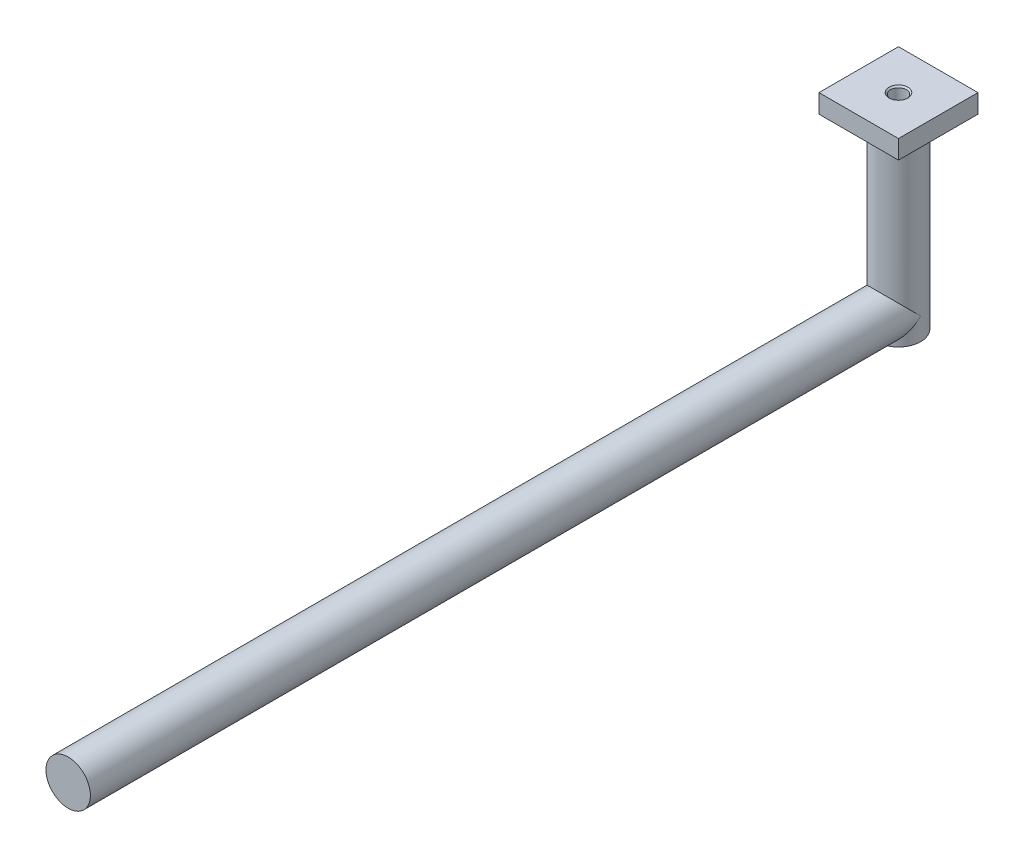
SolidWorks part; units mm, degrees
ref_plane "Front Plane" through (0, 0, 0) normal (0, 0, 1) x (1, 0, 0)
ref_plane "Top Plane" through (0, 0, 0) normal (0, 1, 0) x (1, 0, 0)
ref_plane "Right Plane" through (0, 0, 0) normal (1, 0, 0) x (0, 0, -1)
sketch "Sketch2" plane through (0, 0, 0) normal (0, 0, 1) x (1, 0, 0)
  circle A0 centre (0, 0) radius 9.5
  dimension "D1" = 19
extrude "Boss-Extrude1" add sketch "Sketch2" along normal blind 355
sketch "Sketch3" plane through (0, 0, 0) normal (0, 1, 0) x (1, 0, 0)
  circle A0 centre (0, 0) radius 9.5
  dimension "D1" = 19
extrude "Boss-Extrude2" add sketch "Sketch3" along normal blind 70
extrude "Boss-Extrude3" add sketch "Sketch3<2>" against normal blind 9.5
sketch "Sketch3<2>" plane through (0, 0, 0) normal (0, 1, 0) x (1, 0, 0) same geometry as "Sketch3"
sketch "Sketch5" plane through (0, 70, 0) normal (0, 1, 0) x (1, 0, 0)
  line L0 (-17, 17) -> (17, 17)
  line L5 (-17, 17) -> (-17, -17)
  line L6 (17, 17) -> (17, -17)
  line L7 (-17, -17) -> (17, -17)
  line L8 (-17, 17) -> (17, -17) construction
  line L9 (17, 17) -> (-17, -17) construction
  point P1 (0, 0)
  dimension "D1" = 34
  dimension "D2" = 34
extrude "Boss-Extrude4" add sketch "Sketch5" along normal blind 8
hole_wizard "M8x1.25 Tapped Hole1" positions "3DSketch1" profile "Sketch6" tap size "M8x1.25" standard "ANSI Metric" end condition through all
sketch3d "3DSketch1"
  line L0 (-17, 78, -17) -> (17, 78, 17) construction
  line L2 (-17, 78, 17) -> (17, 78, -17) construction
  point P0 (0, 78, 0)
sketch "Sketch6" plane through (0, 78, 0) normal (1, 0, 0) x (0, 0, 1)
  line L0 (0, 0) -> (0, 87.5)
  line L1 (0, 87.5) -> (3.4, 87.5)
  line L2 (3.4, 87.5) -> (3.4, 0.625)
  line L3 (3.4, 0.625) -> (4.025, 0)
  line L5 (4.025, 0) -> (0, 0)
  line L6 (-3.4, 0.625) -> (-4.025, 0) construction
  line L11 (0, -6.35) -> (0, 107.95) construction
  dimension "Thru Tap Drill Dia." = 6.8
  dimension "Thru Tap Drill Depth" = 87.5
  dimension "Near C'Sink Dia." = 8.05
  dimension "Near C'Sink Angle" = 90
cosmetic thread "Hole Thread1" parameters "D2"=8
